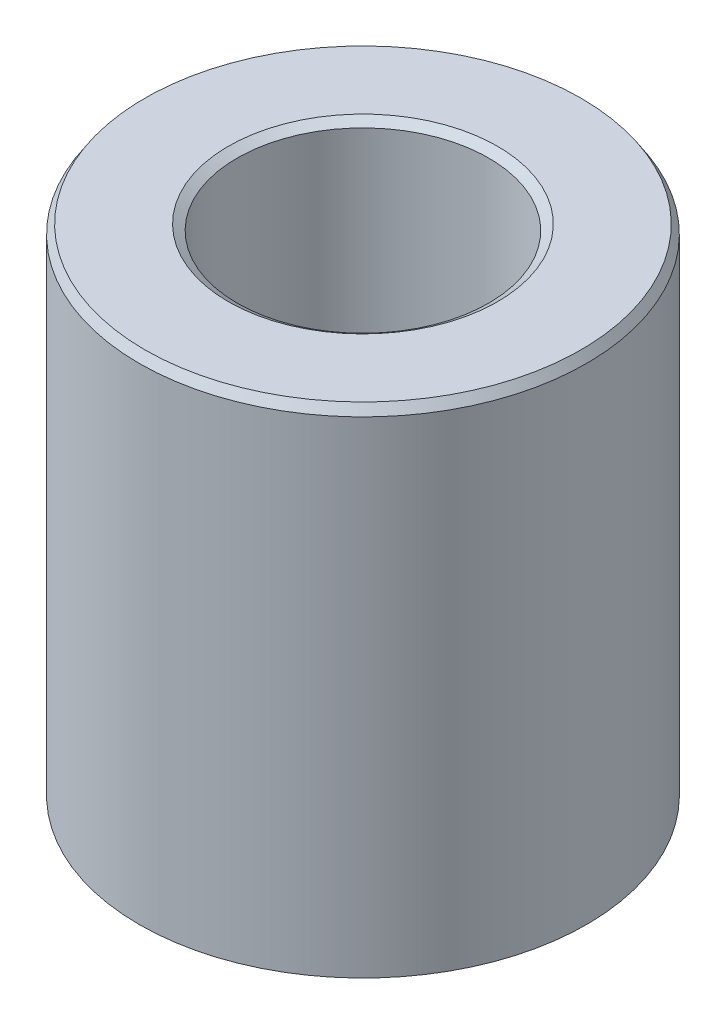
SolidWorks part; units mm, degrees
ref_plane "Front Plane" through (0, 0, 0) normal (0, 0, 1) x (1, 0, 0)
ref_plane "Top Plane" through (0, 0, 0) normal (0, 1, 0) x (1, 0, 0)
ref_plane "Right Plane" through (0, 0, 0) normal (1, 0, 0) x (0, 0, -1)
sketch "Sketch1" plane through (0, 0, 0) normal (0, 1, 0) x (1, 0, 0)
  circle A0 centre (0, 0) radius 32.5
  dimension "SLEEVE_OD" = 65
extrude "Boss-Extrude1" add sketch "Sketch1" along normal blind 72.711
sketch "Sketch2" plane through (0, 0, 0) normal (0, 1, 0) x (1, 0, 0)
  circle A0 centre (0, 0) radius 18.267
  dimension "BORE_D" = 36.534
extrude "Cut-Extrude1" cut sketch "Sketch2" along normal through all
chamfer "Chamfer1" distance 1.2904 angle 32.737 4 edges at (0, 72.711, 18.267) (0, 0, 18.267) (0, 0, 32.5) (0, 72.711, 32.5) first distance on face at (0, 72.711, 18.267) first distance on face at (0, 0, 18.267) first distance on face at (0, 72.711, 32.5)
